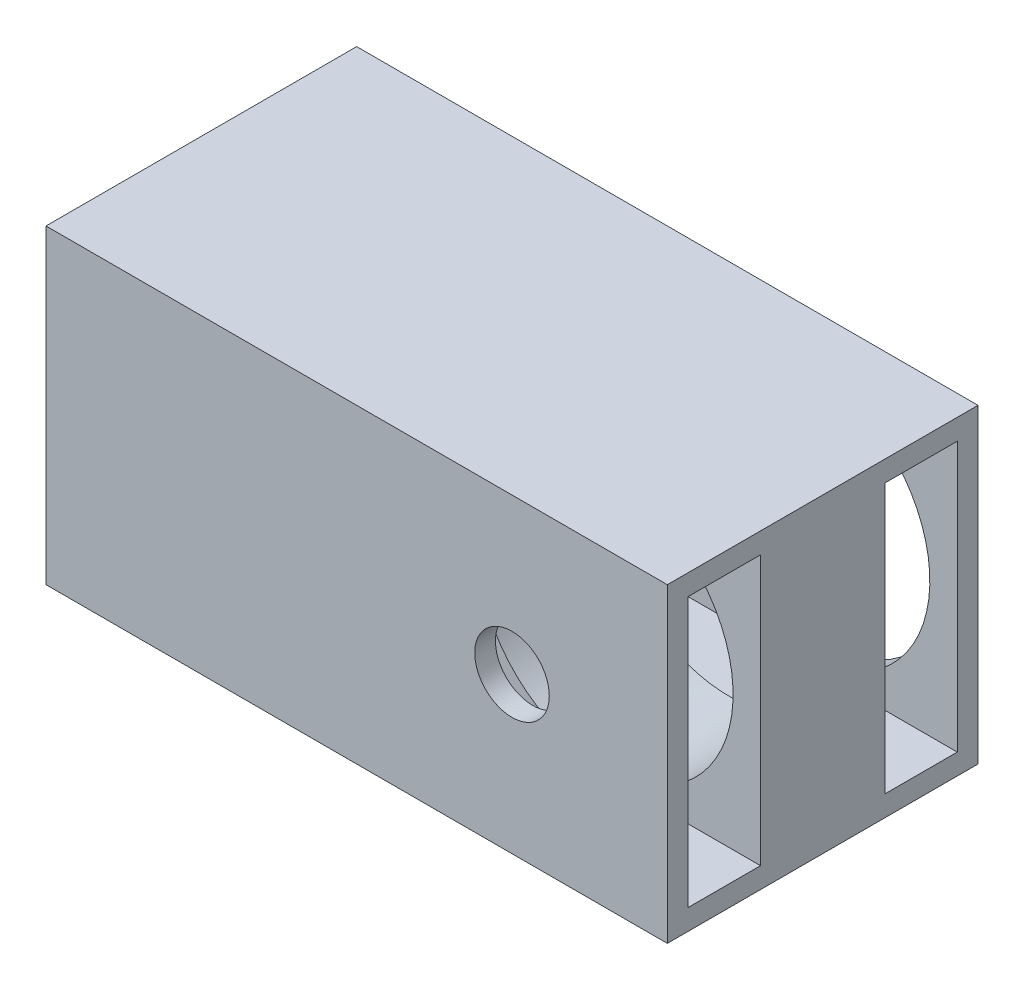
SolidWorks part; units mm, degrees
ref_plane "Front Plane" through (0, 0, 0) normal (0, 0, 1) x (1, 0, 0)
ref_plane "Top Plane" through (0, 0, 0) normal (0, 1, 0) x (1, 0, 0)
ref_plane "Right Plane" through (0, 0, 0) normal (1, 0, 0) x (0, 0, -1)
sketch "Sketch1" plane through (0, 0, 0) normal (1, 0, 0) x (0, 0, -1)
  line L1 (-15, -15) -> (15, -15)
  line L2 (-15, -15) -> (-15, 15)
  line L3 (-15, 15) -> (15, 15)
  line L4 (15, -15) -> (15, 15)
  line L5 (-15, -15) -> (15, 15) construction
  line L6 (-15, 15) -> (15, -15) construction
  line L11 (-5.1844, 5.1844) -> (5.1844, -5.1844) construction
  line L12 (-5.1844, -5.1844) -> (5.1844, 5.1844) construction
  line L13 (-13, 13) -> (-6, 13)
  line L14 (-13, 13) -> (-13, -13)
  line L15 (-13, -13) -> (-6, -13)
  line L16 (-6, 13) -> (-6, -13)
  line L17 (13, 13) -> (6, 13)
  line L18 (13, 13) -> (13, -13)
  line L19 (13, -13) -> (6, -13)
  line L20 (6, 13) -> (6, -13)
  point P0 (0, 0)
  point P7 (0, 0)
  dimension "D1" = 30
  dimension "D2" = 30
  dimension "D3" = 2
  dimension "D4" = 7
  dimension "D5" = 2
  dimension "D6" = 7
  dimension "D7" = 2
  dimension "D8" = 2
extrude "Boss-Extrude3" add sketch "Sketch1" along normal blind 60
sketch "Sketch6" plane through (0, 0, -15) normal (0, 0, -1) x (-1, 0, 0)
  line L0 (-60, -15) -> (-60, 15) construction
  circle A0 centre (-45, 0) radius 12.35
  dimension "D2" = 24.7
  dimension "D1" = 15
extrude "Cut-Extrude5" cut sketch "Sketch6" against normal blind 23
sketch "Sketch8" plane through (0, 0, 15) normal (0, 0, 1) x (1, 0, 0)
  line L0 (60, 15) -> (60, -15) construction
  circle A0 centre (45, 0) radius 3.6
  dimension "D2" = 7.2
  dimension "D1" = 15
extrude "Cut-Extrude6" cut sketch "Sketch8" against normal blind 17
